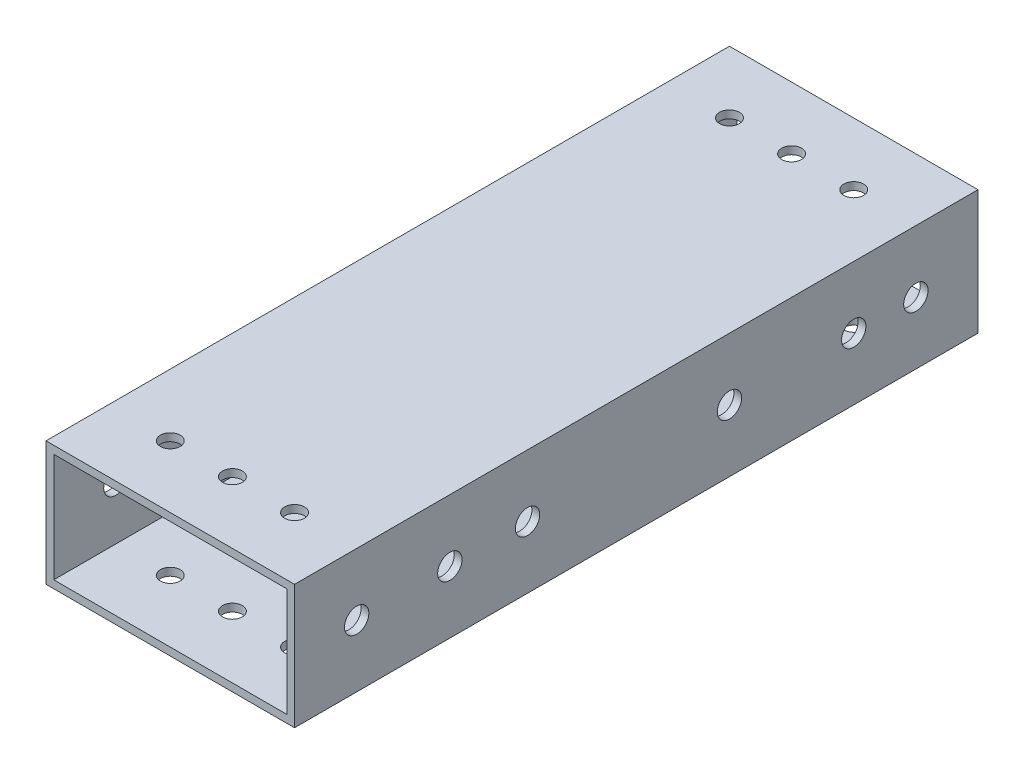
SolidWorks part; units mm, degrees
material "6061-T6 (SS)"
ref_plane "Front Plane" through (0, 0, 0) normal (0, 0, 1) x (1, 0, 0)
ref_plane "Top Plane" through (0, 0, 0) normal (0, 1, 0) x (1, 0, 0)
ref_plane "Right Plane" through (0, 0, 0) normal (1, 0, 0) x (0, 0, -1)
sketch "Sketch1" plane through (0, 0, 0) normal (0, 0, 1) x (1, 0, 0)
  line L0 (-23.8125, 11.1125) -> (23.8125, 11.1125)
  line L1 (-25.4, -12.7) -> (25.4, -12.7)
  line L2 (-25.4, -12.7) -> (-25.4, 12.7)
  line L3 (-25.4, 12.7) -> (25.4, 12.7)
  line L4 (25.4, -12.7) -> (25.4, 12.7)
  line L5 (-25.4, -12.7) -> (25.4, 12.7) construction
  line L6 (-25.4, 12.7) -> (25.4, -12.7) construction
  line L7 (23.8125, -11.1125) -> (23.8125, 11.1125)
  line L8 (-23.8125, -11.1125) -> (23.8125, -11.1125)
  line L9 (-23.8125, -11.1125) -> (-23.8125, 11.1125)
  point P0 (0, 0)
  dimension "D1" = 50.8
  dimension "D2" = 25.4
  dimension "D3" = 1.5875
extrude "Boss-Extrude1" add sketch "Sketch1" along normal mid plane 139.7
sketch "Sketch2" plane through (0, 12.7, 0) normal (0, 1, 0) x (1, 0, 0)
  line L0 (25.4, 69.85) -> (-25.4, 69.85) construction
  line L1 (25.4, 0) -> (-25.4, 0) construction
  line L2 (25.4, -69.85) -> (25.4, 69.85) construction
  line L3 (-25.4, -69.85) -> (-25.4, 69.85) construction
  circle A0 centre (-12.7, 57.15) radius 2.0193
  circle A1 centre (0, 57.15) radius 2.0193
  circle A2 centre (12.7, 57.15) radius 2.0193
  circle A3 centre (12.7, -57.15) radius 2.0193
  circle A4 centre (0, -57.15) radius 2.0193
  circle A5 centre (-12.7, -57.15) radius 2.0193
  dimension "D1" = 4.0386
  dimension "D2" = 12.7
  dimension "D3" = 12.7
  dimension "D4" = 12.7
extrude "Cut-Extrude1" cut sketch "Sketch2" against normal through all
sketch "Sketch3" plane through (25.4, 0, 0) normal (1, 0, 0) x (0, 0, -1)
  line L0 (0, 12.7) -> (0, -12.7) construction
  line L1 (-69.85, 12.7) -> (69.85, 12.7) construction
  line L2 (-69.85, -12.7) -> (69.85, -12.7) construction
  line L3 (-69.85, -12.7) -> (-69.85, 12.7) construction
  line L5 (69.85, -12.7) -> (69.85, 12.7) construction
  circle A8 centre (57.15, 0) radius 2.4892
  circle A9 centre (44.45, 0) radius 2.4892
  circle A10 centre (19.05, 0) radius 2.4892
  circle A11 centre (-57.15, 0) radius 2.4892
  circle A14 centre (-38.1, 0) radius 2.4892
  circle A15 centre (-22.225, 0) radius 2.4892
  dimension "D1" = 12.7
  dimension "D3" = 15.875
  dimension "D8" = 4.9784
  dimension "D2" = 31.75
  dimension "D4" = 25.4
  dimension "D7" = 25.4
extrude "Cut-Extrude2" cut sketch "Sketch3" against normal through all
